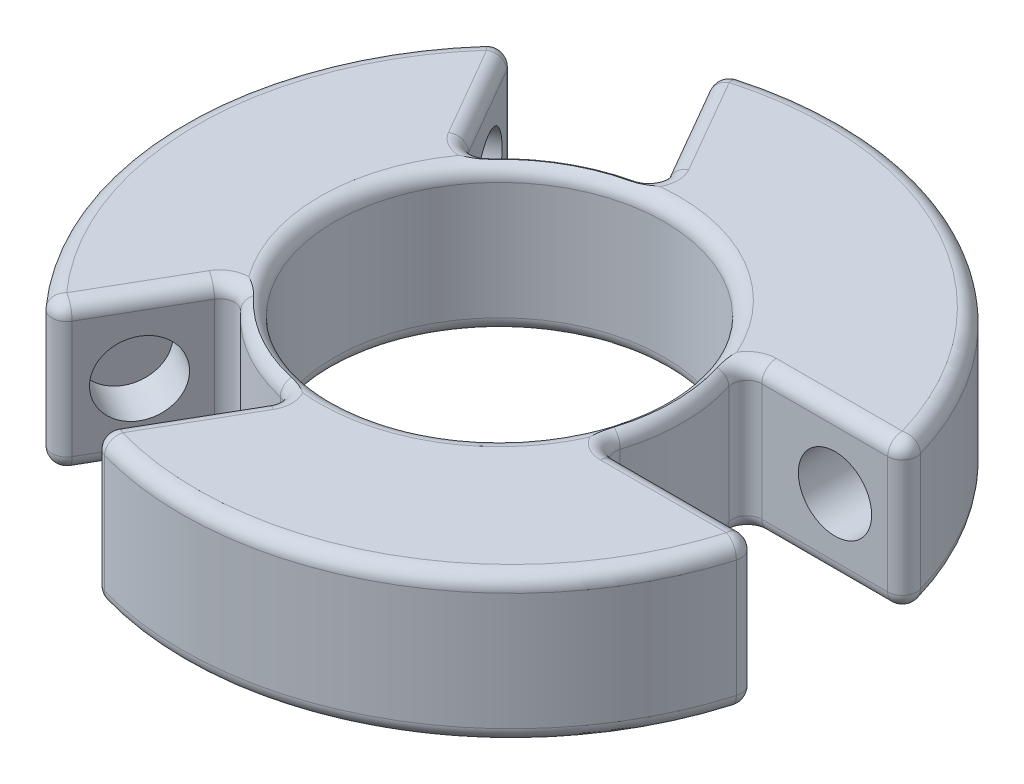
SolidWorks part; units mm, degrees
ref_plane "Front Plane" through (0, 0, 0) normal (0, 0, 1) x (1, 0, 0)
ref_plane "Top Plane" through (0, 0, 0) normal (0, 1, 0) x (1, 0, 0)
ref_plane "Right Plane" through (0, 0, 0) normal (1, 0, 0) x (0, 0, -1)
sketch "Sketch1" plane through (0, 0, 0) normal (0, 1, 0) x (1, 0, 0)
  line L0 (0, 0) -> (22.5, 0) construction
  line L1 (25.7876, -10) -> (42.9609, -10)
  line L2 (25.7876, 10) -> (42.9609, 10)
  line L3 (0, 10) -> (72.0182, 10) construction
  line L4 (0, 0) -> (72.0182, 0) construction
  line L5 (0, -10) -> (72.0182, -10) construction
  line L6 (-4.2335, -27.3327) -> (-11.7647, -40.3771)
  line L7 (-21.5541, -17.3327) -> (-28.6648, -29.6489)
  line L8 (-21.5541, 17.3327) -> (-28.6648, 29.6489)
  line L9 (-4.2335, 27.3327) -> (-11.7647, 40.3771)
  arc A0 (-18.3537, -16.9747) -> (-5.5237, -24.3821) centre (0, 0) ccw
  circle A1 centre (0, 0) radius 22.5
  arc A3 (44.8815, 12.5581) -> (-10.5769, 43.3016) centre (1.6693, 0) ccw
  arc A4 (-31.8883, 29.9814) -> (-31.8883, -29.9814) centre (1.6693, 0) ccw
  arc A5 (-10.5769, -43.3016) -> (44.8815, -12.5581) centre (1.6693, 0) ccw
  arc A6 (-5.5237, 24.3821) -> (-18.3537, 16.9747) centre (0, 0) ccw
  arc A7 (23.8774, -7.4074) -> (23.8774, 7.4074) centre (0, 0) ccw
  arc A8 (-4.2335, -27.3327) -> (-5.5237, -24.3821) centre (-5.9656, -26.3327) ccw
  arc A9 (-21.5541, -17.3327) -> (-18.3537, -16.9747) centre (-19.822, -18.3327) cw
  arc A10 (25.7876, -10) -> (23.8774, -7.4074) centre (25.7876, -8) cw
  arc A11 (25.7876, 10) -> (23.8774, 7.4074) centre (25.7876, 8) ccw
  arc A12 (-4.2335, 27.3327) -> (-5.5237, 24.3821) centre (-5.9656, 26.3327) cw
  arc A13 (-21.5541, 17.3327) -> (-18.3537, 16.9747) centre (-19.822, 18.3327) ccw
  arc A14 (-11.7647, 40.3771) -> (-10.5769, 43.3016) centre (-10.0327, 41.3771) cw
  arc A15 (44.8815, 12.5581) -> (42.9609, 10) centre (42.9609, 12) cw
  arc A16 (44.8815, -12.5581) -> (42.9609, -10) centre (42.9609, -12) ccw
  arc A17 (-10.5769, -43.3016) -> (-11.7647, -40.3771) centre (-10.0327, -41.3771) cw
  arc A18 (-31.8883, -29.9814) -> (-28.6648, -29.6489) centre (-30.3969, -28.6489) ccw
  arc A19 (-28.6648, 29.6489) -> (-31.8883, 29.9814) centre (-30.3969, 28.6489) ccw
  point P28 (22.9129, -10)
  point P47 (-30.003, 31.9667)
  dimension "D1" = 50
  dimension "D2" = 45
  dimension "D3" = 90
  dimension "D4" = 10
  dimension "D7" = 2
  dimension "D5" = 10
  dimension "D6" = 3
extrude "Boss-Extrude1" add sketch "Sketch1" along normal blind 20
sketch "Sketch2" plane through (8.6603, 0, -5) normal (-0.866, 0, 0.5) x (0.5, 0, 0.866)
  line L0 (-40.85, 20) -> (-25.7876, 20) construction
  circle A0 centre (-33.2725, 10) radius 5
  dimension "D1" = 10
  dimension "D2" = 10
extrude "Cut-Extrude1" cut sketch "Sketch2" against normal blind 9 and the other way blind 29
pattern_circular "CirPattern1" count 3 over 360 about axis through (1.6693, 20, 0) along (0, -1, 0) of "Cut-Extrude1"
fillet "Fillet2" radius 2 25 edges at (0, 20, 22.5) (-12.5, 20, 21.6506) (-20.0443, 20, 16.3451) (-25.1094, 20, 23.4908) (-30.1917, 20, 30.6384) (-43.3307, 20, 0) (-30.1917, 20, -30.6384) (-25.1094, 20, -23.4908) (-20.0443, 20, -16.3451) (-12.5, 20, -21.6506) (-4.1331, 20, -25.5314) (-7.9991, 20, -33.8549) (-11.8857, 20, -42.1297) (23.487, 20, -39.3572) (44.5604, 20, -10.7992) (34.3743, 20, -10) (24.1774, 20, -9.1863) (25, 20, 0) (24.1774, 20, 9.1863) (34.3743, 20, 10) (44.5604, 20, 10.7992) (23.487, 20, 39.3572) (-11.8857, 20, 42.1297) (-7.9991, 20, 33.8549) (-4.1331, 20, 25.5314)
fillet "Fillet3" radius 2 25 edges at (0, 0, 22.5) (-7.9991, 0, 33.8549) (-11.8857, 0, 42.1297) (23.487, 0, 39.3572) (44.5604, 0, 10.7992) (34.3743, 0, 10) (24.1774, 0, 9.1863) (25, 0, 0) (24.1774, 0, -9.1863) (34.3743, 0, -10) (44.5604, 0, -10.7992) (23.487, 0, -39.3572) (-11.8857, 0, -42.1297) (-7.9991, 0, -33.8549) (-4.1331, 0, -25.5314) (-12.5, 0, -21.6506) (-20.0443, 0, -16.3451) (-25.1094, 0, -23.4908) (-30.1917, 0, -30.6384) (-43.3307, 0, 0) (-30.1917, 0, 30.6384) (-25.1094, 0, 23.4908) (-20.0443, 0, 16.3451) (-12.5, 0, 21.6506) (-4.1331, 0, 25.5314)
